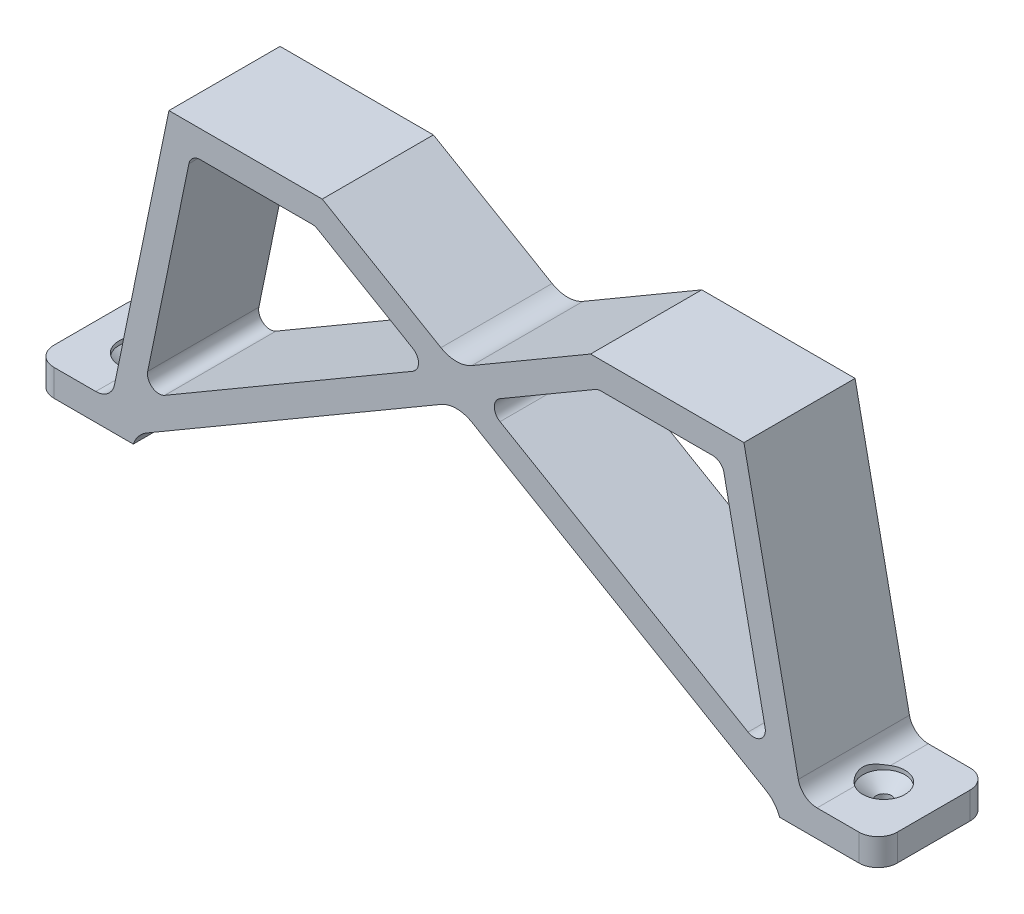
SolidWorks part; units mm, degrees
material "ABS"
ref_plane "Front" through (0, 0, 0) normal (0, 0, 1) x (1, 0, 0)
ref_plane "Top" through (0, 0, 0) normal (0, 1, 0) x (1, 0, 0)
ref_plane "Right" through (0, 0, 0) normal (1, 0, 0) x (0, 0, -1)
sketch "Esquisse1" plane through (0, 0, 0) normal (0, 0, 1) x (1, 0, 0)
  line L0 (-110, 0) -> (-90, 0)
  line L1 (-90, 0) -> (-75, 73)
  line L2 (-75, 73) -> (-35, 73)
  line L3 (0, 73) -> (0, 0) construction
  line L4 (-90, 0) -> (90, 0) construction
  line L6 (-35, 73) -> (90, 0)
  dimension "D1" = 73
  dimension "D2" = 15
  dimension "D3" = 20
  dimension "D4" = 150
  dimension "D5" = 40
extrude "Extru.-Mince1" add sketch "Esquisse1" along normal mid plane 29 thin thin type one direction wall 7
fillet "Congé1" radius 5 2 edges at (-110, -3.5, -14.5) (-110, -3.5, 14.5)
fillet "Congé2" radius 5 1 edges at (-90, 0, 0)
sketch "Esquisse4" plane through (0, -7, 0) normal (0, -1, 0) x (1, 0, 0)
  line L0 (-75, 14.5) -> (-75, -14.5) construction
  circle A0 centre (-97, 0) radius 2
  dimension "D1" = 4
  dimension "D2" = 22
extrude "Enlèv. mat.-Extru.1" cut sketch "Esquisse4" against normal blind 3
sketch "Esquisse5" plane through (0, -4, 0) normal (0, -1, 0) x (1, 0, 0)
  circle A0 centre (-97, 0) radius 5.5
  dimension "D1" = 11
extrude "Enlèv. mat.-Extru.2" cut sketch "Esquisse5" against normal through all
chamfer "Chanfrein1" distance 3.5 angle 40 1 edges at (-91.5, -4, 0) first distance on face at (-95, -4, 0)
mirror "Symétrie1" about plane through (0, 0, 0) normal (1, 0, 0) of bodies 104
fillet "Congé3" radius 8 4 edges at (0, 52.56, 0) (0, 44.4537, 0) (83.7721, -4.4692, 0) (-83.7721, -4.4692, 0)
fillet "Congé4" radius 3 8 edges at (69.2921, 66, 0) (6.9403, 48.5069, 0) (81.8793, 4.7425, 0) (36.8943, 66, 0) (-36.8943, 66, 0) (-81.8793, 4.7425, 0) (-6.9403, 48.5069, 0) (-69.2921, 66, 0)
